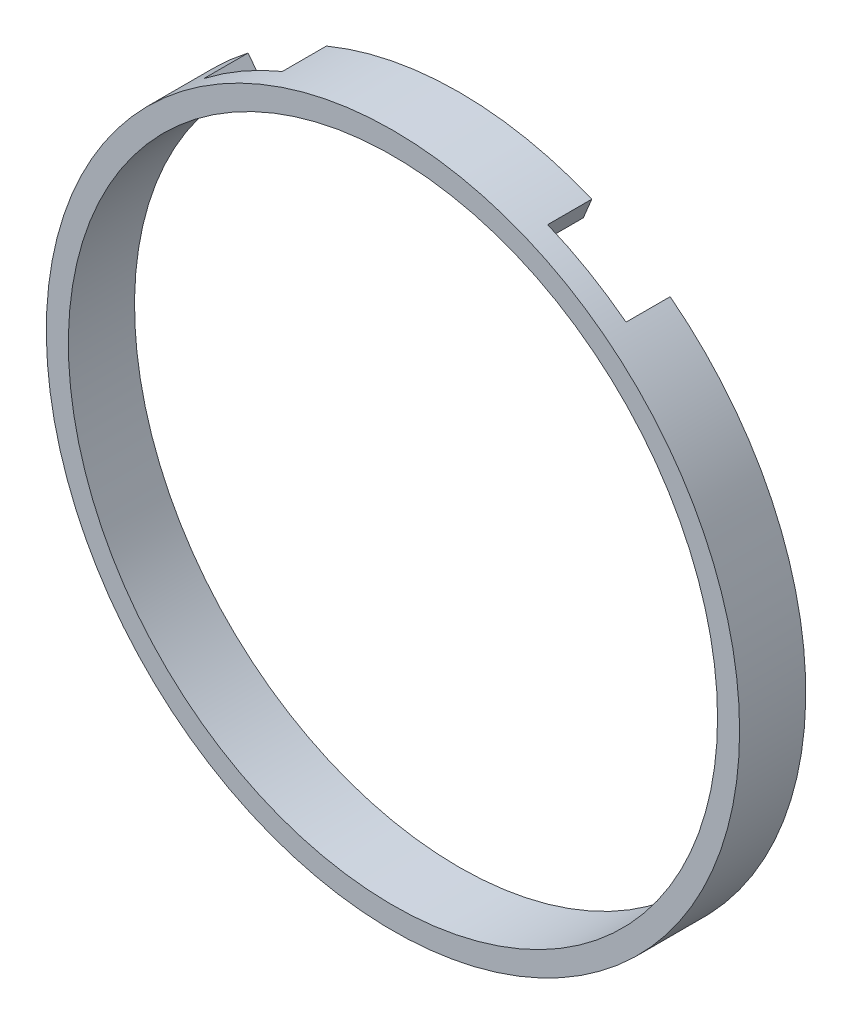
SolidWorks part; units mm, degrees
material "Acrylic (Medium-high impact)"
ref_plane "Front Plane" through (0, 0, 0) normal (0, 0, 1) x (1, 0, 0)
ref_plane "Top Plane" through (0, 0, 0) normal (0, 1, 0) x (1, 0, 0)
ref_plane "Right Plane" through (0, 0, 0) normal (1, 0, 0) x (0, 0, -1)
sketch "Sketch1" plane through (0, 0, 0) normal (0, 0, 1) x (1, 0, 0)
  circle A0 centre (0, 0) radius 24.9555
  circle A1 centre (0, 0) radius 24.9555 construction
  circle A2 centre (0, 0) radius 23.368
  dimension "D1" = 1.5875
extrude "Boss-Extrude1" add sketch "Sketch1" along normal blind 4.7625
sketch "Sketch2" plane through (0, 0, 0) normal (0, 0, -1) x (-1, 0, 0)
  line L0 (0, 0) -> (0, 24.9555) construction
  line L1 (0, 0) -> (12.4778, 21.6121) construction
  line L2 (9.5501, 23.0559) -> (8.9425, 21.5892)
  line L3 (8.9425, 21.5892) -> (0, 0) construction
  line L4 (15.1919, 19.7985) -> (14.2255, 18.5391)
  line L5 (14.2255, 18.5391) -> (0, 0) construction
  circle A0 centre (0, 0) radius 24.9555 construction
  circle A1 centre (0, 0) radius 23.368 construction
  arc A2 (8.9425, 21.5892) -> (14.2255, 18.5391) centre (0, 0) cw
  arc A3 (9.5501, 23.0559) -> (15.1919, 19.7985) centre (0, 0) cw
  dimension "D1" = 30
  dimension "D2" = 7.5
  dimension "D3" = 15
extrude "Cut-Extrude1" cut sketch "Sketch2" against normal blind 3.175
mirror "Mirror1" about plane through (0, 0, 0) normal (1, 0, 0) of "Cut-Extrude1"
